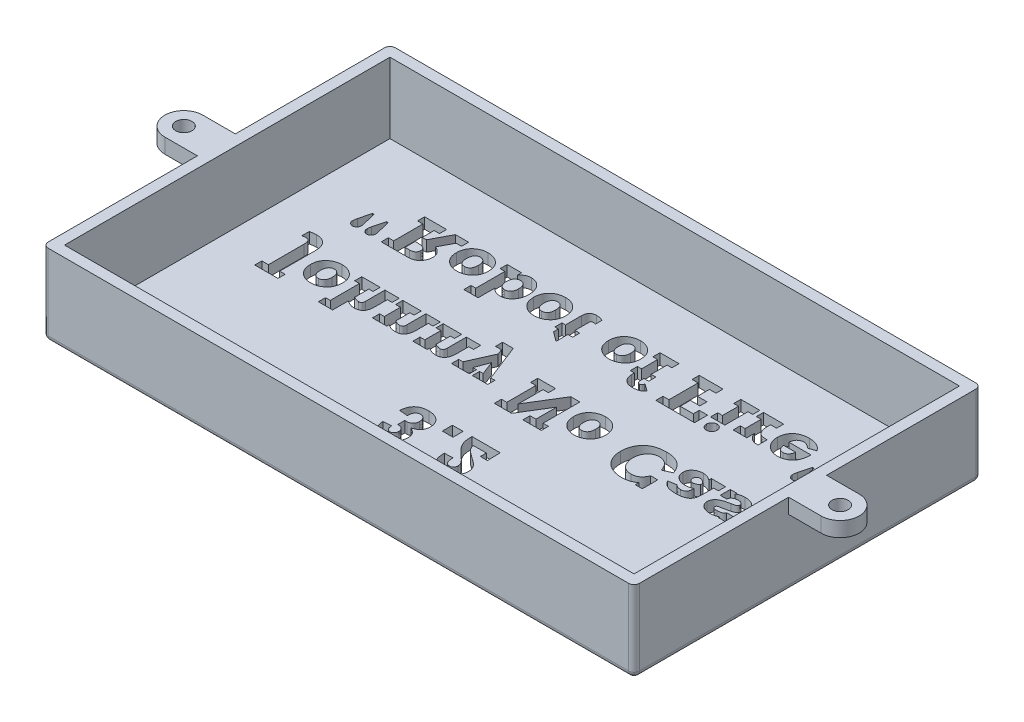
SolidWorks part; units mm, degrees
ref_plane "Front Plane" through (0, 0, 0) normal (0, 0, 1) x (1, 0, 0)
ref_plane "Top Plane" through (0, 0, 0) normal (0, 1, 0) x (1, 0, 0)
ref_plane "Right Plane" through (0, 0, 0) normal (1, 0, 0) x (0, 0, -1)
sketch "Sketch1" plane through (0, 0, 0) normal (0, 1, 0) x (1, 0, 0)
  line L1 (-52.5, 30) -> (52.5, 30)
  line L2 (-52.5, 30) -> (-52.5, -30)
  line L3 (-52.5, -30) -> (52.5, -30)
  line L4 (52.5, 30) -> (52.5, -30)
  point P4 (-52.5, 0)
  point P6 (0, 30)
  dimension "D1" = 105
  dimension "D2" = 60
extrude "Boss-Extrude1" add sketch "Sketch1" along normal blind 2
sketch "Sketch2" plane through (0, 2, 0) normal (0, 1, 0) x (1, 0, 0)
  line L0 (-54.5, 32) -> (-54.5, -32)
  line L1 (-52.5, 30) -> (52.5, 30)
  line L2 (-52.5, 30) -> (-52.5, -30)
  line L3 (-52.5, -30) -> (52.5, -30)
  line L4 (52.5, 30) -> (52.5, -30)
  line L5 (-54.5, -32) -> (54.5, -32)
  line L6 (54.5, 32) -> (54.5, -32)
  line L7 (-54.5, 32) -> (54.5, 32)
  dimension "D1" = 2
extrude "Boss-Extrude2" add sketch "Sketch2" along normal blind 13 and the other way blind 2 separate body
fillet "Fillet1" radius 1 8 edges at (0, 0, -32) (-54.5, 7.5, -32) (-54.5, 0, 0) (-54.5, 7.5, 32) (0, 0, 32) (54.5, 7.5, 32) (54.5, 0, 0) (54.5, 7.5, -32)
sketch "Sketch3" plane through (54.5, 0, 0) normal (1, 0, 0) x (0, 0, -1)
  line L0 (-31, 15) -> (31, 15) construction
  line L1 (-3.5, 15) -> (3.5, 15)
  line L2 (-3.5, 15) -> (-3.5, 12.25)
  line L3 (-3.5, 12.25) -> (3.5, 12.25)
  line L4 (3.5, 15) -> (3.5, 12.25)
  point P6 (0, 15)
  dimension "D1" = 2.75
  dimension "D2" = 7
extrude "Boss-Extrude3" add sketch "Sketch3" along normal blind 6
sketch "Sketch4" plane through (0, 12.25, 0) normal (0, -1, 0) x (1, 0, 0)
  line L0 (60.5, 3.5) -> (60.5, -3.5) construction
  line L1 (60.5, 3.5) -> (60.5, -3.5)
  arc A0 (60.5, 3.5) -> (60.5, -3.5) centre (60.5, 0) cw
extrude "Boss-Extrude4" add sketch "Sketch4" against normal blind 2.75
sketch "Sketch5" plane through (0, 12.25, 0) normal (0, -1, 0) x (1, 0, 0)
  circle A0 centre (60.5, 0) radius 1.5
  dimension "D1" = 3
extrude "Cut-Extrude1" cut sketch "Sketch5" against normal blind 2.75
mirror "Mirror1" about plane through (0, 0, 0) normal (1, 0, 0) of "Boss-Extrude3", "Boss-Extrude4", "Cut-Extrude1"
sketch "Sketch9" plane through (0, 0, 0) normal (0, -1, 0) x (1, 0, 0)
  line L2 (-45, 10) -> (45, 10) construction
  line L3 (52.5, -30) -> (-52.5, -30) construction
  text T0 "3.2\r\nJohnny No Cash\r\n\"Robot of Fire\"" font "Rockwell" height 8
  point P10 (0, 10)
  dimension "D1" = 90
  dimension "D2" = 40
extrude "Cut-Extrude3" cut sketch "Sketch9" against normal through all
